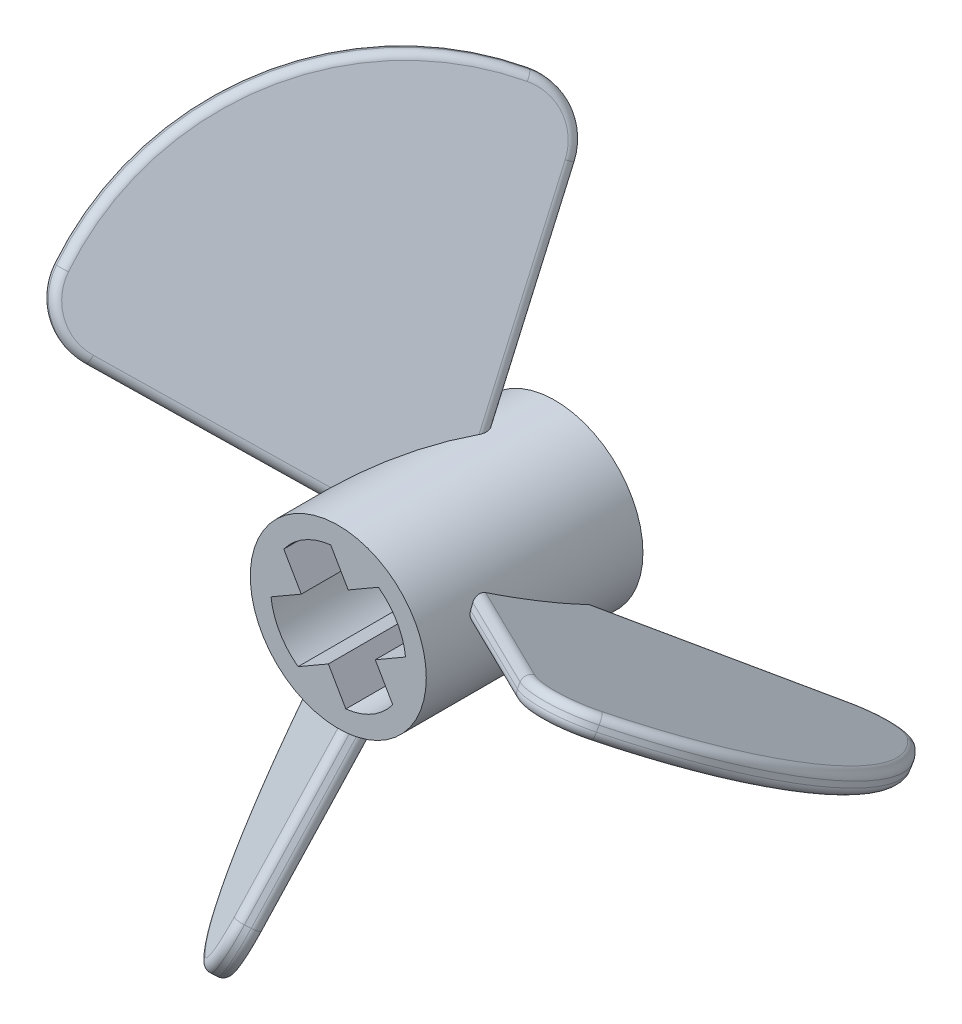
SolidWorks part; units mm, degrees
ref_plane "Front Plane" through (0, 0, 0) normal (0, 0, 1) x (1, 0, 0)
ref_plane "Top Plane" through (0, 0, 0) normal (0, 1, 0) x (1, 0, 0)
ref_plane "Right Plane" through (0, 0, 0) normal (1, 0, 0) x (0, 0, -1)
sketch "Sketch1" plane through (0, 0, 0) normal (0, 0, 1) x (1, 0, 0)
  circle A0 centre (0, 0) radius 3.25
  dimension "D1" = 6.5
extrude "Boss-Extrude1" add sketch "Sketch1" along normal mid plane 8
ref_plane "Plane1" through (12, 0, 0) normal (1, 0, 0) x (0, 0, -1)
ref_axis "Axis1" through (2.75, 0, 0) along (-1, 0, 0)
ref_plane "Plane2" through (0, 0, 0) normal (0, 0.866, -0.5) x (-1, 0, 0)
sketch "Sketch6" plane through (0, 0, 0) normal (0, 0.866, -0.5) x (-1, 0, 0)
  line L0 (0, 0) -> (-10, 8)
  line L1 (0, 0) -> (-10, -8)
  arc A0 (-10, -8) -> (-10, 8) centre (-4, 0) cw
  dimension "D4" = 10
  dimension "D1" = 16
  dimension "D2" = 10
  dimension "D3" = 8
extrude "Boss-Extrude4" add sketch "Sketch6" along normal mid plane 0.8
fillet "Fillet1" radius 2 2 edges at (10, -4, -6.9282) (10, 4, 6.9282)
pattern_circular "CirPattern2" count 3 over 360 about axis through (0, 0, 4) along (0, 0, -1) of "Boss-Extrude4", "Fillet1"
sketch "Sketch7" plane through (0, 0, 4) normal (0, 0, 1) x (1, 0, 0)
  line L0 (1.4843, 2.0117) -> (0.366, 1.366)
  line L1 (2.4843, 0.2796) -> (1.366, -0.366)
  line L2 (-0.2796, 2.4843) -> (0.366, 1.366)
  line L3 (-2.0117, 1.4843) -> (-1.366, 0.366)
  line L4 (1.366, -0.366) -> (2.0117, -1.4843)
  line L5 (-1.366, 0.366) -> (-2.4843, -0.2796)
  line L6 (-0.366, -1.366) -> (0.2796, -2.4843)
  line L7 (-0.366, -1.366) -> (-1.4843, -2.0117)
  line L8 (0, 0) -> (-3.9924, 6.915) construction
  line L9 (0, 0) -> (0, 6.4328) construction
  arc A1 (-0.2796, 2.4843) -> (-2.0117, 1.4843) centre (0, 0) ccw
  arc A2 (-2.4843, -0.2796) -> (-1.4843, -2.0117) centre (0, 0) ccw
  arc A3 (2.4843, 0.2796) -> (1.4843, 2.0117) centre (0, 0) ccw
  arc A4 (0.2796, -2.4843) -> (2.0117, -1.4843) centre (0, 0) ccw
  dimension "D1" = 5
  dimension "D2" = 1
  dimension "D3" = 2
  dimension "D4" = 1
  dimension "D5" = 2
  dimension "D6" = 30
extrude "Cut-Extrude1" cut sketch "Sketch7" against normal up to next
fillet "Fillet2" radius 0.3 30 edges at (-1.2059, -6.1142, 4.2863) (-2.1492, -10.4008, 6.5835) (-7.3, -11.9512, 0.2) (-8.5327, -6.7153, -6.1835) (-0.5875, -6.3333, 3.8035) (-1.5492, -10.7472, 6.1835) (-6.7, -12.2976, -0.2) (-7.9327, -7.0617, -6.5835) (-5.191, 3.6755, 3.8035) (-8.5327, 6.7153, 6.1835) (-7.3, 11.9512, -0.2) (-1.2059, 6.1142, -4.2863) (-0.5875, 6.3333, -3.8035) (-4.6921, 4.1014, 4.2863) (-7.9327, 7.0617, 6.5835) (-6.7, 12.2976, 0.2) (5.7786, -2.6578, -3.8035) (10.082, -4.0319, -6.1835) (14, -0.3464, 0.2) (10.082, 3.3391, 6.5835) (5.898, -2.0128, -4.2863) (10.082, -3.3391, -6.5835) (14, 0.3464, -0.2) (10.082, 4.0319, 6.1835) (-5.191, -3.6755, -3.8035) (-4.6921, -4.1014, -4.2863) (-2.1492, 10.4008, -6.5835) (-1.5492, 10.7472, -6.1835) (5.898, 2.0128, 4.2863) (5.7786, 2.6578, 3.8035)
